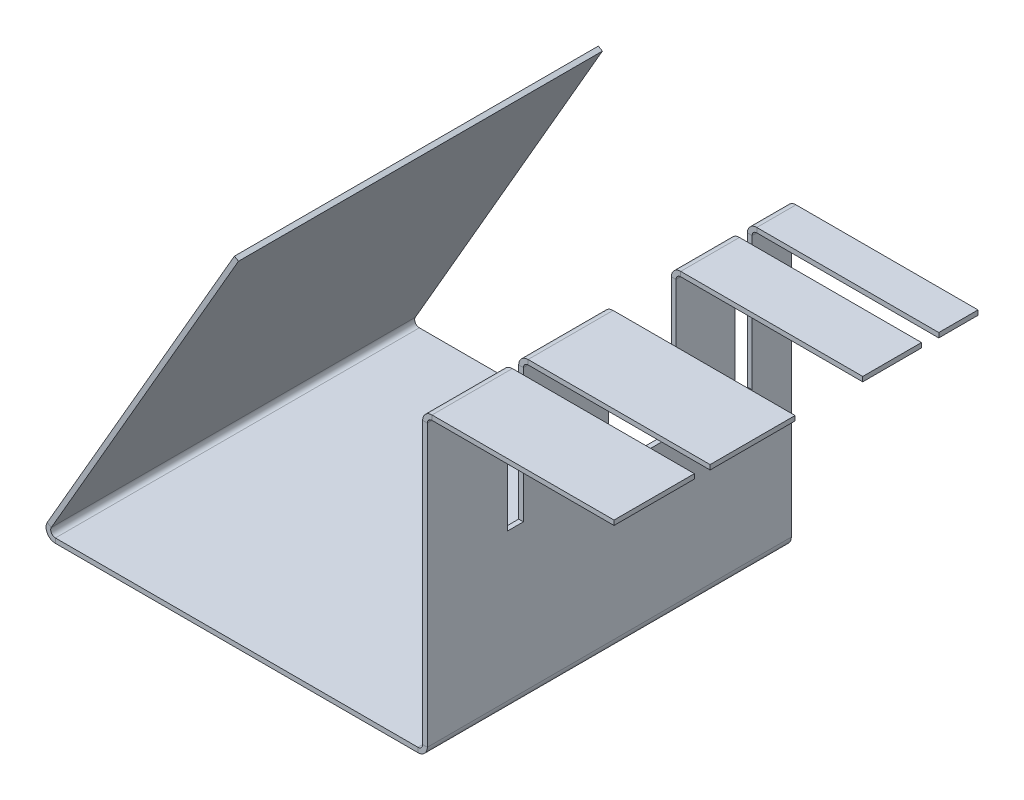
SolidWorks part; units mm, degrees
note: The reader was unsure of these and kept them because the rebuilt part matched: flange length of "Edge-Flange1", "Edge-Flange2", "Edge-Flange3".
ref_plane "Front Plane" through (0, 0, 0) normal (0, 0, 1) x (1, 0, 0)
ref_plane "Top Plane" through (0, 0, 0) normal (0, 1, 0) x (1, 0, 0)
ref_plane "Right Plane" through (0, 0, 0) normal (1, 0, 0) x (0, 0, -1)
other "Configuration Table"
sketch "Sketch1" plane through (0, 0, 0) normal (0, 1, 0) x (1, 0, 0)
  line L1 (-45.2875, 23.017) -> (13.5437, 23.017)
  line L2 (-45.2875, 23.017) -> (-45.2875, -34.0271)
  line L3 (-45.2875, -34.0271) -> (13.5437, -34.0271)
  line L4 (13.5437, 23.017) -> (13.5437, -34.0271)
sheet metal parameters "Sheet-Metal1" thickness 0.7366 parameters "D1"=0.7366
base flange "Base-Flange1" sketch "Sketch1" thickness 0.7366 reverse thickness direction no parameters "D1"=0.7366
edge flange "Edge-Flange1" sketch "Sketch6" flange angle 90 flange length 46.2098 flange position material outside bend radius 0.7366 thickness 0.7366 relief rectangular parameters "D6"=10
sketch "Sketch6" plane through (13.5437, 0, 0) normal (1, 0, 0) x (0, 0, -1)
  line L0 (-34.0271, 0) -> (23.017, 0) construction
  line L1 (-34.0271, 0) -> (23.017, 0)
  line L2 (-34.0271, 0) -> (-34.0271, 45.4732)
  line L3 (-34.0271, 45.4732) -> (23.017, 45.4732)
  line L4 (23.017, 45.4732) -> (23.017, 0)
bend "EdgeBend1" bend radius 0.7366 bend angle 90 parameters "D5"=1
sketch "Sketch7" plane through (13.5437, 0, 0) normal (-1, 0, 0) x (0, 0, 1)
  line L1 (-16.8728, 49.5376) -> (-14.16, 49.5376)
  line L2 (-16.8728, 49.5376) -> (-16.8728, 23.8069)
  line L3 (-16.8728, 23.8069) -> (-14.16, 23.8069)
  line L4 (-14.16, 49.5376) -> (-14.16, 23.8069)
  line L5 (-4.9528, 50.4484) -> (5.6518, 50.4484)
  line L6 (-4.9528, 50.4484) -> (-4.9528, 23.8069)
  line L7 (-4.9528, 23.8069) -> (5.6518, 23.8069)
  line L8 (5.6518, 50.4484) -> (5.6518, 23.8069)
  line L9 (18.9693, 52.5792) -> (21.4355, 52.5792)
  line L10 (18.9693, 52.5792) -> (18.9693, 23.8069)
  line L11 (18.9693, 23.8069) -> (21.4355, 23.8069)
  line L12 (21.4355, 52.5792) -> (21.4355, 23.8069)
extrude "Cut-Extrude1" cut sketch "Sketch7" against normal blind 10 normal cut yes
edge flange "Edge-Flange2" sketch "Sketch10" flange angle 60 flange length 61.2098 flange position material outside bend radius 0.7366 thickness 0.7366 relief rectangular parameters "D6"=10
sketch "Sketch10" plane through (-45.2875, 0, 0) normal (-0.866, 0.5, 0) x (0, 0, 1)
  line L0 (-23.017, 0) -> (34.0271, 0) construction
  line L1 (-23.017, 0) -> (34.0271, 0)
  line L2 (-23.017, 0) -> (-23.017, 59.934)
  line L3 (-23.017, 59.934) -> (34.0271, 59.934)
  line L4 (34.0271, 59.934) -> (34.0271, 0)
bend "EdgeBend2" bend radius 0.7366 bend angle 120 parameters "D5"=2
edge flange "Edge-Flange3" sketch "Sketch19" flange profiles "Sketch19", "Sketch20", "Sketch21", "Sketch22" flange angle 90 flange length 30 flange position material outside bend radius 0.7366 thickness 0.7366 relief rectangular parameters "D6"=10, "D8"=1
sketch "Sketch19" plane through (14.2803, 45.4732, 0) normal (0, -1, 0) x (0, 0, -1)
  line L2 (16.8728, 0) -> (16.8728, 29.2634)
  line L3 (16.8728, 29.2634) -> (23.017, 29.2634)
  line L4 (23.017, 29.2634) -> (23.017, 0)
  line L6 (23.017, 0) -> (16.8728, 0) construction
  line L7 (23.017, 0) -> (16.8728, 0)
sketch "Sketch20" plane through (14.2803, 45.4732, 0) normal (0, -1, 0) x (0, 0, -1)
  line L2 (14.16, 0) -> (14.16, 29.2634)
  line L3 (14.16, 29.2634) -> (4.9528, 29.2634)
  line L4 (4.9528, 29.2634) -> (4.9528, 0)
  line L5 (14.16, 0) -> (4.9528, 0) construction
  line L6 (14.16, 0) -> (4.9528, 0)
sketch "Sketch21" plane through (14.2803, 45.4732, 0) normal (0, -1, 0) x (0, 0, -1)
  line L2 (-5.6518, 0) -> (-5.6518, 29.2634)
  line L3 (-5.6518, 29.2634) -> (-18.9693, 29.2634)
  line L4 (-18.9693, 29.2634) -> (-18.9693, 0)
  line L5 (-5.6518, 0) -> (-18.9693, 0) construction
  line L6 (-5.6518, 0) -> (-18.9693, 0)
sketch "Sketch22" plane through (14.2803, 45.4732, 0) normal (0, -1, 0) x (0, 0, -1)
  line L1 (-21.4355, 0) -> (-34.0271, 0) construction
  line L2 (-34.0271, 0) -> (-34.0271, 29.2634)
  line L3 (-34.0271, 29.2634) -> (-21.4355, 29.2634)
  line L4 (-21.4355, 29.2634) -> (-21.4355, 0)
  line L5 (-21.4355, 0) -> (-34.0271, 0)
bend "EdgeBend3" bend radius 0.7366 bend angle 90 parameters "D5"=3
bend "EdgeBend4" bend radius 0.7366 bend angle 90 parameters "D5"=4
bend "EdgeBend5" bend radius 0.7366 bend angle 90 parameters "D5"=5
bend "EdgeBend6" bend radius 0.7366 bend angle 90 parameters "D5"=6
flat pattern "Flat-Pattern1" [suppressed]
sketch "Bend-Lines1" plane through (0, 0, 0) normal (0, 1, 0) x (-1, 0, 0)
sketch3d "Bounding-Box1" [suppressed]
  line L0 (129.3929, 0, 0) -> (0, 0, 0) construction
  line L1 (129.3929, -69.1754, 0) -> (0, -69.1754, 0) construction
  line L2 (129.3929, 0, 0) -> (129.3929, -69.1754, 0) construction
  line L3 (0, 0, 0) -> (0, -69.1754, 0) construction
bend of the flat pattern "Flatten-<EdgeBend1>1"
bend of the flat pattern "Flatten-<EdgeBend2>1"
bend of the flat pattern "Flatten-<EdgeBend3>1"
bend of the flat pattern "Flatten-<EdgeBend4>1"
bend of the flat pattern "Flatten-<EdgeBend5>1"
bend of the flat pattern "Flatten-<EdgeBend6>1"
